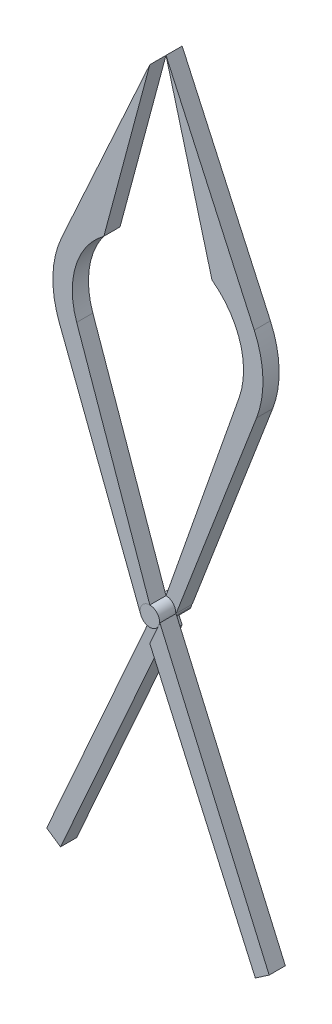
SolidWorks part; units mm, degrees
ref_plane "Front Plane" through (0, 0, 0) normal (0, 0, 1) x (1, 0, 0)
ref_plane "Top Plane" through (0, 0, 0) normal (0, 1, 0) x (1, 0, 0)
ref_plane "Right Plane" through (0, 0, 0) normal (1, 0, 0) x (0, 0, -1)
sketch "Sketch1" plane through (0, 0, 0) normal (0, 0, 1) x (1, 0, 0)
  line L0 (0, 1072.4264) -> (0, 36.2132) construction
  line L1 (0, 0) -> (-50000, 0) construction
  line L2 (0, 36.2132) -> (-7.1138, 9.664)
  line L3 (0, 36.2132) -> (-13.6527, 6.2132)
  line L4 (0, 36.2132) -> (7.1138, 9.664)
  line L5 (0, 36.2132) -> (13.6527, 6.2132)
  line L6 (-11.321, -3.9793) -> (0, -36.1869)
  line L7 (-14.0037, -5.3755) -> (-1.3964, -38.2187)
  line L9 (11.321, -3.9793) -> (0, -36.1869)
  line L10 (14.0037, -5.3755) -> (1.3964, -38.2187)
  line L11 (0, 0) -> (0, -50000) construction
  line L17 (1.3964, -38.2187) -> (-16.3179, -78.0055)
  line L18 (-1.3964, -38.2187) -> (-18.4612, -76.5468)
  line L19 (-18.4612, -76.5468) -> (-16.3179, -78.0055)
  line L20 (18.4612, -76.5468) -> (16.3179, -78.0055)
  line L21 (18.4612, -76.5468) -> (1.4957, -37.6826)
  line L22 (16.3179, -78.0055) -> (-1.3664, -38.2911)
  arc A0 (-13.6527, 6.2132) -> (-14.0037, -5.3755) centre (0, 0) ccw
  arc A1 (-7.1138, 9.664) -> (-11.321, -3.9793) centre (0, 0) ccw
  arc A2 (11.321, -3.9793) -> (7.1138, 9.664) centre (0, 0) ccw
  arc A3 (14.0037, -5.3755) -> (13.6527, 6.2132) centre (0, 0) ccw
  circle A4 centre (0, -37.6826) radius 1.4957
  dimension "D1" = 30
  dimension "D2" = 30
  dimension "D5" = 24
  dimension "D4" = 42
  dimension "D6" = 2.9915
  dimension "D3" = 30
  dimension "D9" = 2.5926
  dimension "D10" = 135
  dimension "D12" = 39.7869
extrude "Boss-Extrude30" add sketch "Sketch1" along normal mid plane 5 contours A4 L17 region at (0, -37.6826, 0)
extrude "Boss-Extrude31" add sketch "Sketch1<9>" against normal blind 2.5 contours A4 L10 A3 L5 L4 A2 L9 region at (6.1389, 20.9003, 0)
sketch "Sketch1<9>" plane through (0, 0, 0) normal (0, 0, 1) x (1, 0, 0) same geometry as "Sketch1"
extrude "Boss-Extrude34" add sketch "Sketch1<11>" along normal blind 2.5 separate body contours A4 L6 A1 L2 L3 A0 L7 region at (-4.2903, 23.1351, 0)
sketch "Sketch1<11>" plane through (0, 0, 0) normal (0, 0, 1) x (1, 0, 0) same geometry as "Sketch1"
extrude "Boss-Extrude39" add sketch "Sketch1<15>" along normal blind 2.5 separate body contours A4 L17 L22 L20 L10 region at (8.9381, -58.0763, 0)
sketch "Sketch1<15>" plane through (0, 0, 0) normal (0, 0, 1) x (1, 0, 0) same geometry as "Sketch1"
extrude "Boss-Extrude40" add sketch "Sketch1<16>" against normal blind 2.5 separate body contours A4 L18 L19 L17 L22 region at (-9.051, -58.5241, 0)
sketch "Sketch1<16>" plane through (0, 0, 0) normal (0, 0, 1) x (1, 0, 0) same geometry as "Sketch1"
